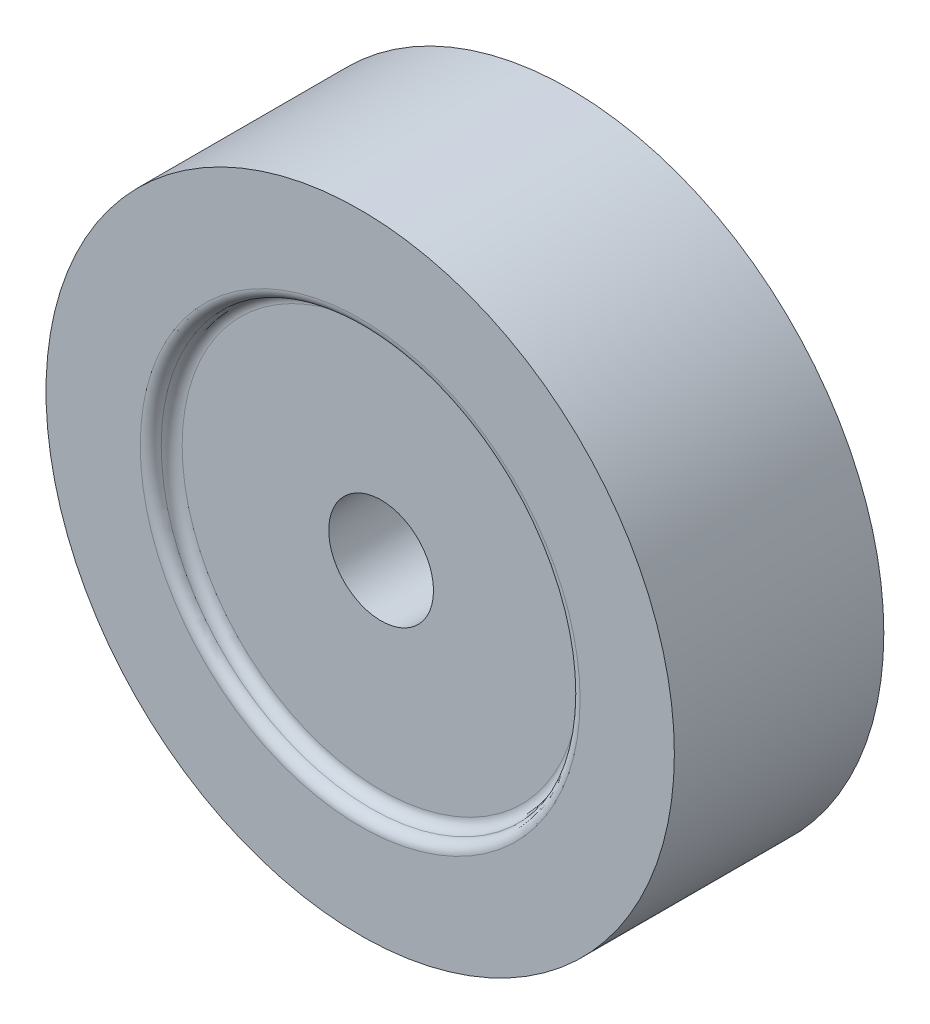
SolidWorks part; units mm, degrees
ref_plane "Front Plane" through (0, 0, 0) normal (0, 0, 1) x (1, 0, 0)
ref_plane "Top Plane" through (0, 0, 0) normal (0, 1, 0) x (1, 0, 0)
ref_plane "Right Plane" through (0, 0, 0) normal (1, 0, 0) x (0, 0, -1)
sketch "Sketch1" plane through (0, 0, 0) normal (0, 0, 1) x (1, 0, 0)
  circle A0 centre (0, 0) radius 30
  dimension "D1" = 60
extrude "Boss-Extrude1" add sketch "Sketch1" along normal mid plane 20
sketch "Sketch2" plane through (0, 0, 10) normal (0, 0, 1) x (1, 0, 0)
  circle A0 centre (0, 0) radius 20
  dimension "D1" = 20
extrude "Cut-Extrude1" cut sketch "Sketch2" against normal blind 2
mirror "Mirror1" about plane through (0, 0, 0) normal (0, 0, 1) of "Cut-Extrude1"
fillet "Fillet1" radius 1 4 edges at (20, 0, 8) (20, 0, 10) (20, 0, -8) (20, 0, -10)
sketch "Sketch3" plane through (0, 0, 8) normal (0, 0, 1) x (1, 0, 0)
  circle A0 centre (0, 0) radius 5
  dimension "D1" = 5
extrude "Cut-Extrude2" cut sketch "Sketch3" against normal up to next
